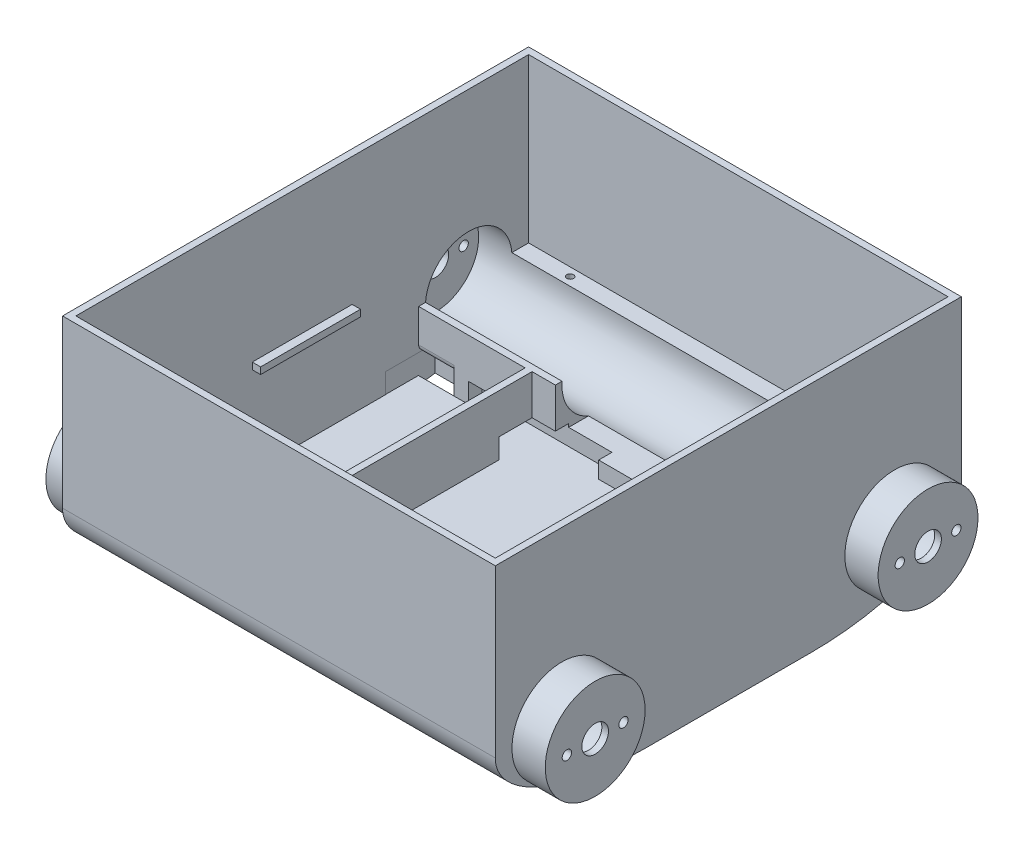
SolidWorks part; units mm, degrees
ref_plane "Спереди" through (0, 0, 0) normal (0, 0, 1) x (1, 0, 0)
ref_plane "Сверху" through (0, 0, 0) normal (0, 1, 0) x (1, 0, 0)
ref_plane "Справа" through (0, 0, 0) normal (1, 0, 0) x (0, 0, -1)
sketch "Эскиз1" plane through (0, 0, 0) normal (0, 1, 0) x (1, 0, 0)
  line L1 (-65, 70) -> (65, 70)
  line L2 (-65, 70) -> (-65, -70)
  line L3 (-65, -70) -> (65, -70)
  line L4 (65, 70) -> (65, -70)
  dimension "D1" = 130
  dimension "D2" = 65
  dimension "D3" = 140
  dimension "D4" = 70
extrude "Бобышка-Вытянуть1" add sketch "Эскиз1" along normal blind 35 and the other way blind 35
sketch "Эскиз2" plane through (65, 0, 0) normal (1, 0, 0) x (0, 0, -1)
  line L0 (-70, -15) -> (70, -15) construction
  line L1 (-70, -35) -> (-70, 35) construction
  line L2 (70, -35) -> (70, 35) construction
  line L3 (-70, -35) -> (70, -35) construction
  line L4 (-25, -35) -> (25, -35)
  line L5 (-70, -40.7424) -> (-70, -15)
  line L7 (-70, -40.7424) -> (70, -40.7424)
  line L8 (70, -40.7424) -> (70, -15)
  ellipse E0 centre (-25, -15) end of major axis (-70, -15) minor radius 20 (-70, -15) -> (-25, -35) ccw
  ellipse E1 centre (25, -15) end of major axis (-20, -15) minor radius 20 (70, -15) -> (25, -35) cw
  point P10 (-25, -15)
  point P11 (25, -15)
  dimension "D1" = 20
  dimension "D2" = 50
  dimension "D3" = 25
  dimension "D4" = 25
  dimension "D5" = 25
extrude "Вырез-Вытянуть1" cut sketch "Эскиз2" against normal blind 130
sketch "Эскиз3" plane through (0, 35, 0) normal (0, 1, 0) x (1, 0, 0)
  line L0 (-65, 70) -> (-65, -70) construction
  line L1 (-63, 68) -> (63, 68)
  line L2 (-63, 68) -> (-63, -68)
  line L3 (-63, -68) -> (63, -68)
  line L4 (63, 68) -> (63, -68)
  line L5 (65, -70) -> (65, 70) construction
  line L6 (-65, -70) -> (65, -70) construction
  line L7 (65, 70) -> (-65, 70) construction
  dimension "D1" = 2
  dimension "D2" = 2
  dimension "D3" = 2
  dimension "D4" = 2
extrude "Вырез-Вытянуть2" cut sketch "Эскиз3" against normal blind 49
sketch "Эскиз4" plane through (0, 0, 0) normal (1, 0, 0) x (0, 0, -1)
  line L0 (-70, -15) -> (70, -15) construction
  circle A0 centre (-50, -15) radius 13
  circle A1 centre (50, -15) radius 13
  ellipse E0 centre (25, -15) end of major axis (70, -15) minor radius 20 (25, -35) -> (70, -15) ccw construction
  point P10 (-50, -15)
  point P11 (50, -15)
  dimension "D3" = 26
  dimension "D4" = 26
  dimension "D1" = 20
  dimension "D2" = 20
extrude "Вырез-Вытянуть3" cut sketch "Эскиз4" against normal blind 63 and the other way blind 63
sketch "Эскиз7" plane through (65, 0, 0) normal (1, 0, 0) x (0, 0, -1)
  line L0 (-70, -15) -> (70, -15) construction
  line L1 (-70, -15) -> (-70, 35) construction
  line L2 (70, -15) -> (70, 35) construction
  line L3 (-70, 35) -> (70, 35) construction
  circle A0 centre (-58.5, -15) radius 1.4
  circle A1 centre (-50, -15) radius 4
  circle A2 centre (-41.5, -15) radius 1.4
  circle A3 centre (41.5, -15) radius 1.4
  circle A4 centre (50, -15) radius 4
  circle A5 centre (58.5, -15) radius 1.4
  point P8 (-50, -15)
  point P9 (50, -15)
  point P10 (-58.5, -15)
  point P11 (-41.5, -15)
  point P12 (58.5, -15)
  point P13 (41.5, -15)
  dimension "D8" = 2.8
  dimension "D9" = 2.8
  dimension "D10" = 2.8
  dimension "D11" = 2.8
  dimension "D12" = 8
  dimension "D13" = 8
  dimension "D1" = 50
  dimension "D2" = 20
  dimension "D3" = 20
  dimension "D4" = 8.5
  dimension "D5" = 8.5
  dimension "D6" = 8.5
  dimension "D7" = 8.5
sketch "Эскиз8" plane through (65, 0, 0) normal (1, 0, 0) x (0, 0, -1)
  line L0 (-70, -15) -> (-70, 35) construction
  circle A0 centre (-50, -15) radius 15
  circle A1 centre (50, -15) radius 15
  dimension "D1" = 20
  dimension "D2" = 30
  dimension "D3" = 20
extrude "Бобышка-Вытянуть3" add sketch "Эскиз8" along normal blind 10
mirror "Зеркальное отражение2" about plane through (0, 0, 0) normal (1, 0, 0) of "Бобышка-Вытянуть3"
extrude "Вырез-Вытянуть6" cut sketch "Эскиз7" along normal blind 32 and the other way blind 160
sketch "Эскиз9" plane through (63, 0, 0) normal (-1, 0, 0) x (0, 0, 1)
  circle A0 centre (-50, -15) radius 13
  circle A1 centre (50, -15) radius 13
  dimension "D1" = 26
  dimension "D2" = 26
extrude "Вырез-Вытянуть7" cut sketch "Эскиз9" against normal blind 10 and the other way blind 136
sketch "Эскиз10" plane through (0, -14, 0) normal (0, 1, 0) x (1, 0, 0)
  line L0 (-63, -37.0385) -> (63, -37.0385) construction
  line L1 (-63, 34.9615) -> (-31, 34.9615)
  line L2 (-63, 34.9615) -> (-63, -35.0385)
  line L3 (-63, -35.0385) -> (-31, -35.0385)
  line L4 (-31, 34.9615) -> (-31, -35.0385)
  line L7 (63, 37.0385) -> (-63, 37.0385) construction
  line L8 (-63, 37.0385) -> (-63, -37.0385) construction
  line L9 (63, -37.0385) -> (63, 37.0385) construction
  line L10 (31, 34.9615) -> (63, 34.9615)
  line L11 (31, 34.9615) -> (31, -35.0385)
  line L12 (31, -35.0385) -> (63, -35.0385)
  line L13 (63, 34.9615) -> (63, -35.0385)
  dimension "D1" = 70
  dimension "D2" = 2
  dimension "D3" = 2.077
  dimension "D4" = 32
  dimension "D5" = 0
  dimension "D6" = 70
  dimension "D7" = 32
  dimension "D8" = 0
  dimension "D9" = 2
extrude "Вырез-Вытянуть8" cut sketch "Эскиз10" against normal blind 18
sketch "Эскиз11" plane through (0, -14, 0) normal (0, 1, 0) x (1, 0, 0)
  line L0 (63, 37.0385) -> (-63, 37.0385) construction
  line L1 (-29, 35.0385) -> (29, 35.0385)
  line L2 (-29, 35.0385) -> (-29, -35.0385)
  line L3 (-29, -35.0385) -> (29, -35.0385)
  line L4 (29, 35.0385) -> (29, -35.0385)
  line L7 (-31, -35.0385) -> (-31, 34.9615) construction
  line L8 (31, 34.9615) -> (31, -35.0385) construction
  line L9 (-63, -35.0385) -> (-31, -35.0385) construction
  dimension "D1" = 2
  dimension "D2" = 0
  dimension "D3" = 2
  dimension "D4" = 2
  dimension "D5" = 58
  dimension "D6" = 70.077
extrude "Вырез-Вытянуть9" cut sketch "Эскиз11" against normal blind 18
sketch "Эскиз13" plane through (0, -14, 0) normal (0, 1, 0) x (1, 0, 0)
  line L3 (-22, 35.0385) -> (22, 35.0385)
  line L4 (-22, 35.0385) -> (-22, 50)
  line L5 (29, 35.0385) -> (-29, 35.0385) construction
  line L6 (-29, -35.0385) -> (29, -35.0385) construction
  line L8 (-22, 50) -> (22, 50)
  line L9 (22, 35.0385) -> (22, 50)
  line L10 (-22, -35.0385) -> (22, -35.0385)
  line L12 (-22, -35.0385) -> (-22, -50)
  line L13 (-22, -50) -> (22, -50)
  line L14 (22, -35.0385) -> (22, -50)
  dimension "D1" = 44
  dimension "D2" = 22
  dimension "D3" = 44
  dimension "D4" = 22
  dimension "D5" = 50
  dimension "D6" = 50
extrude "Вырез-Вытянуть11" cut sketch "Эскиз13" against normal blind 13
sketch "Эскиз14" plane through (0, 0, -35.0385) normal (0, 0, 1) x (1, 0, 0)
  line L0 (-63, -32) -> (-63, -14) construction
  line L1 (-9, -26) -> (-48, -26)
  line L2 (-9, -26) -> (-9, -32)
  line L3 (-9, -32) -> (-48, -32)
  line L4 (-48, -26) -> (-48, -32)
  line L5 (-29, -32) -> (-29, -14) construction
  line L6 (29, -32) -> (-29, -32) construction
  line L7 (-31, -32) -> (-31, -14) construction
  line L9 (-63.0555, -32) -> (-52.3555, -32)
  line L10 (-63.0555, -32) -> (-63.0555, -26)
  line L11 (-63.0555, -26) -> (-52.3555, -26)
  line L12 (-52.3555, -32) -> (-52.3555, -26)
  dimension "D1" = 15
  dimension "D2" = 20
  dimension "D3" = 6
  dimension "D4" = 0
  dimension "D5" = 17
  dimension "D6" = 10.7
  dimension "D7" = 6
extrude "Вырез-Вытянуть12" cut sketch "Эскиз14" against normal blind 4 and the other way blind 10
mirror "Зеркальное отражение4" about plane through (0, 0, 0) normal (1, 0, 0) of "Вырез-Вытянуть12"
sketch "Эскиз15" plane through (63, 0, 0) normal (-1, 0, 0) x (0, 0, 1)
  line L0 (35.0385, -14) -> (-34.9615, -14) construction
  line L1 (-15, -3.5) -> (15, -3.5)
  line L2 (-15, -3.5) -> (-15, -5.5)
  line L3 (-15, -5.5) -> (15, -5.5)
  line L4 (15, -3.5) -> (15, -5.5)
  dimension "D1" = 30
  dimension "D2" = 15
  dimension "D3" = 2
  dimension "D4" = 8.5
extrude "Бобышка-Вытянуть4" add sketch "Эскиз15" along normal blind 2.5
mirror "Зеркальное отражение3" about plane through (0, 0, 0) normal (1, 0, 0) of "Бобышка-Вытянуть4"
sketch "Эскиз16" plane through (0, -14, 0) normal (0, 1, 0) x (1, 0, 0)
  line L0 (-63, 62.9615) -> (63, 62.9615) construction
  line L1 (-63, 68) -> (-63, 62.9615) construction
  circle A0 centre (-48, 65.5015) radius 1
  point P6 (-63, 65.4807)
  dimension "D1" = 2.54
  dimension "D3" = 2
  dimension "D2" = 15
extrude "Вырез-Вытянуть13" cut sketch "Эскиз16" against normal blind 5
mirror "Зеркальное отражение5" about plane through (0, 0, 0) normal (0, 0, 1) of "Вырез-Вытянуть13"
mirror "Зеркальное отражение6" about plane through (0, 0, 0) normal (1, 0, 0) of "Зеркальное отражение5"
sketch "Эскиз17" plane through (0, -32, 0) normal (0, 1, 0) x (1, 0, 0)
  line L1 (-52.3555, 34.9615) -> (-63.0555, 34.9615)
  line L2 (-52.3555, 34.9615) -> (-52.3555, 39.9615)
  line L3 (-52.3555, 39.9615) -> (-63.0555, 39.9615)
  line L4 (-63.0555, 34.9615) -> (-63.0555, 39.9615)
  point P6 (-66.6784, 41.3823)
  dimension "D1" = 5
extrude "Вырез-Вытянуть14" cut sketch "Эскиз17" against normal through all and the other way blind 3
mirror "Зеркальное отражение10" about plane through (0, 0, 0) normal (1, 0, 0) of "Вырез-Вытянуть14"
fillet "Скругление17" radius 2 4 edges at (-57.7055, -29, -39.0385) (-57.6778, -26, -34.9615) (57.6778, -26, -34.9615) (57.7055, -29, -39.0385)
